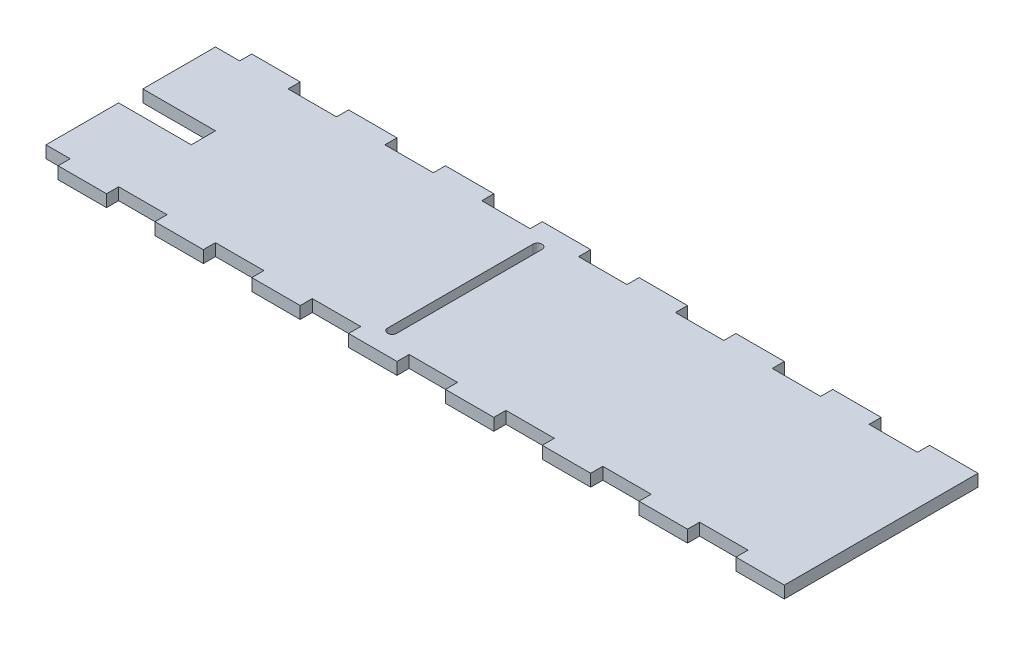
SolidWorks part; units mm, degrees
material "Acrylic (Medium-high impact)"
ref_plane "Front Plane" through (0, 0, 0) normal (0, 0, 1) x (1, 0, 0)
ref_plane "Top Plane" through (0, 0, 0) normal (0, 1, 0) x (1, 0, 0)
ref_plane "Right Plane" through (0, 0, 0) normal (1, 0, 0) x (0, 0, -1)
sketch "Sketch1" plane through (0, 0, 0) normal (0, 1, 0) x (1, 0, 0)
  line L0 (95.25, 0) -> (95.25, -50.8) construction
  line L5 (0, 0) -> (190.5, 0)
  line L6 (0, 0) -> (0, -50.8)
  line L7 (0, -50.8) -> (190.5, -50.8)
  line L8 (190.5, 0) -> (190.5, -50.8)
  line L9 (190.5, -25.4) -> (0, -25.4) construction
  line L14 (12.7, 0) -> (12.7, -3.175)
  line L15 (12.7, -50.8) -> (25.4, -50.8)
  line L16 (12.7, -50.8) -> (12.7, -47.625)
  line L17 (12.7, -47.625) -> (25.4, -47.625)
  line L18 (25.4, -50.8) -> (25.4, -47.625)
  line L19 (12.7, -3.175) -> (25.4, -3.175)
  line L20 (25.4, 0) -> (25.4, -3.175)
  line L21 (38.1, 0) -> (38.1, -3.175)
  line L22 (38.1, -3.175) -> (50.8, -3.175)
  line L23 (50.8, 0) -> (50.8, -3.175)
  line L24 (50.8, -50.8) -> (50.8, -47.625)
  line L25 (38.1, -47.625) -> (50.8, -47.625)
  line L26 (38.1, -50.8) -> (38.1, -47.625)
  line L27 (63.5, 0) -> (63.5, -3.175)
  line L28 (63.5, -3.175) -> (76.2, -3.175)
  line L29 (76.2, 0) -> (76.2, -3.175)
  line L30 (76.2, -50.8) -> (76.2, -47.625)
  line L31 (63.5, -47.625) -> (76.2, -47.625)
  line L32 (63.5, -50.8) -> (63.5, -47.625)
  line L33 (88.9, 0) -> (88.9, -3.175)
  line L34 (88.9, -3.175) -> (101.6, -3.175)
  line L35 (101.6, 0) -> (101.6, -3.175)
  line L36 (101.6, -50.8) -> (101.6, -47.625)
  line L37 (88.9, -47.625) -> (101.6, -47.625)
  line L38 (88.9, -50.8) -> (88.9, -47.625)
  line L39 (114.3, 0) -> (114.3, -3.175)
  line L40 (114.3, -3.175) -> (127, -3.175)
  line L41 (127, 0) -> (127, -3.175)
  line L42 (127, -50.8) -> (127, -47.625)
  line L43 (114.3, -47.625) -> (127, -47.625)
  line L44 (114.3, -50.8) -> (114.3, -47.625)
  line L45 (139.7, 0) -> (139.7, -3.175)
  line L46 (139.7, -3.175) -> (152.4, -3.175)
  line L47 (152.4, 0) -> (152.4, -3.175)
  line L48 (152.4, -50.8) -> (152.4, -47.625)
  line L49 (139.7, -47.625) -> (152.4, -47.625)
  line L50 (139.7, -50.8) -> (139.7, -47.625)
  line L51 (165.1, 0) -> (165.1, -3.175)
  line L52 (165.1, -3.175) -> (177.8, -3.175)
  line L53 (177.8, 0) -> (177.8, -3.175)
  line L54 (177.8, -50.8) -> (177.8, -47.625)
  line L55 (165.1, -47.625) -> (177.8, -47.625)
  line L56 (165.1, -50.8) -> (165.1, -47.625)
  dimension "D1" = 50.8
  dimension "D2" = 190.5
  dimension "D3" = 3.175
  dimension "D4" = 12.7
  dimension "D5" = 12.7
  dimension "D7" = 12.7
  dimension "D6" = 7
extrude "Boss-Extrude1" add sketch "Sketch1" along normal blind 3.175 contours L7 L56 L55 L54 L8 L5 L53 L52 L51 L47 L46 L45 L41 L40 L39 L35 L34 L33 L29 L28 L27 L23 L22 L21 L20 L19 L14 L6 L16 L17 L18 L26 L25 L24 L32 L31 L30 L38 L37 region at (95.25, 0, 25.4)
sketch "Sketch2" plane through (0, 3.175, 0) normal (0, 1, 0) x (1, 0, 0)
  line L2 (0, 0) -> (0, -50.8) construction
  line L3 (0, -28.575) -> (12.7, -28.575)
  line L4 (0, -28.575) -> (0, -22.225)
  line L5 (0, -22.225) -> (12.7, -22.225)
  line L6 (12.7, -28.575) -> (12.7, -22.225)
  point P12 (0, -25.4)
  point P13 (0, -25.4)
  dimension "D3" = 6.35
  dimension "D4" = 12.7
extrude "Cut-Extrude1" cut sketch "Sketch2" against normal through all
sketch "Sketch3" plane through (0, 0, 0) normal (-1, 0, 0) x (0, 0, 1)
  line L1 (3.175, 0) -> (22.225, 0)
  line L2 (3.175, 0) -> (3.175, 3.175)
  line L3 (3.175, 3.175) -> (22.225, 3.175)
  line L4 (22.225, 0) -> (22.225, 3.175)
  line L5 (47.625, 0) -> (28.575, 0)
  line L6 (47.625, 0) -> (47.625, 3.175)
  line L7 (47.625, 3.175) -> (28.575, 3.175)
  line L8 (28.575, 0) -> (28.575, 3.175)
  line L9 (50.8, 3.175) -> (50.8, 0) construction
  line L10 (0, 3.175) -> (0, 0) construction
  line L11 (0, 0) -> (22.225, 0) construction
  dimension "D1" = 3.175
  dimension "D2" = 3.175
extrude "Boss-Extrude2" add sketch "Sketch3" along normal blind 6.35
sketch "Sketch4" plane through (0, 3.175, 0) normal (0, 1, 0) x (1, 0, 0)
  line L0 (166.37, -9.525) -> (166.37, -41.275) construction
  line L1 (167.5689, -9.525) -> (167.5689, -41.275)
  line L2 (165.1711, -9.525) -> (165.1711, -41.275)
  line L3 (190.5, 0) -> (190.5, -50.8) construction
  line L4 (152.4, -50.8) -> (165.1, -50.8) construction
  arc A0 (167.5689, -9.525) -> (165.1711, -9.525) centre (166.37, -9.525) ccw
  arc A1 (165.1711, -41.275) -> (167.5689, -41.275) centre (166.37, -41.275) ccw
  point P2 (166.37, -25.4)
  dimension "D2" = 1.1989
  dimension "D1" = 24.13
  dimension "D3" = 25.4
  dimension "D4" = 31.75
extrude "Cut-Extrude2" [suppressed] cut sketch "Sketch4" against normal up to surface (3.175 mm away)
sketch "Sketch5" plane through (0, 3.175, 0) normal (0, 1, 0) x (1, 0, 0)
  line L0 (81.28, -6.35) -> (81.28, -44.45) construction
  line L1 (82.48, -6.35) -> (82.48, -44.45)
  line L2 (80.08, -6.35) -> (80.08, -44.45)
  line L5 (76.2, -50.8) -> (88.9, -50.8) construction
  arc A0 (82.48, -6.35) -> (80.08, -6.35) centre (81.28, -6.35) ccw
  arc A1 (80.08, -44.45) -> (82.48, -44.45) centre (81.28, -44.45) ccw
  point P2 (81.28, -25.4)
  dimension "D2" = 1.2
  dimension "D1" = 109.22
  dimension "D3" = 38.1
  dimension "D4" = 25.4
extrude "Cut-Extrude4" cut sketch "Sketch5" against normal up to surface (3.175 mm away) contours A1 L1 A0 L2 up to face at (84.0441, 0, 25.4)
sketch "Sketch6" plane through (0, 0, 0) normal (0, -1, 0) x (-1, 0, 0)
  line L0 (-104.14, -44.45) -> (-104.14, -6.35)
  line L5 (-104.14, -44.45) -> (-107.88, -44.45)
  line L6 (-107.88, -44.45) -> (-107.88, -6.35)
  line L7 (-91.44, -44.45) -> (-95.18, -44.45)
  line L8 (-91.44, -44.45) -> (-91.44, -6.35)
  line L9 (-91.44, -6.35) -> (-95.18, -6.35)
  line L10 (-95.18, -44.45) -> (-95.18, -6.35)
  line L11 (-82.48, -44.45) -> (-82.48, -6.35) construction
  line L12 (-104.14, -6.35) -> (-107.88, -6.35)
  line L13 (-116.84, -44.45) -> (-116.84, -6.35)
  line L14 (-116.84, -44.45) -> (-120.58, -44.45)
  line L15 (-120.58, -44.45) -> (-120.58, -6.35)
  line L16 (-116.84, -6.35) -> (-120.58, -6.35)
  line L17 (-129.54, -44.45) -> (-129.54, -6.35)
  line L18 (-129.54, -44.45) -> (-133.28, -44.45)
  line L19 (-133.28, -44.45) -> (-133.28, -6.35)
  line L20 (-129.54, -6.35) -> (-133.28, -6.35)
  line L21 (-142.24, -44.45) -> (-142.24, -6.35)
  line L22 (-142.24, -44.45) -> (-145.98, -44.45)
  line L23 (-145.98, -44.45) -> (-145.98, -6.35)
  line L24 (-142.24, -6.35) -> (-145.98, -6.35)
  arc A0 (-80.08, -6.35) -> (-82.48, -6.35) centre (-81.28, -6.35) ccw construction
  arc A1 (-82.48, -44.45) -> (-80.08, -44.45) centre (-81.28, -44.45) ccw construction
  point P25 (-81.28, -5.15)
  point P31 (-93.31, -44.45)
  dimension "D5" = 0
  dimension "D1" = 5
  dimension "D2" = 0
  dimension "D3" = 10.16
  dimension "D4" = 12.7
  dimension "D6" = 8.96
extrude "Boss-Extrude3" add sketch "Sketch6" along normal blind 2.54 contours L13 L16 L15 L14 | L0 L12 L6 L5 | L8 L9 L10 L7 | L21 L24 L23 L22 | L17 L20 L19 L18
fillet "Fillet1" radius 5.08 10 edges at (93.31, -2.54, 6.35) (106.01, -2.54, 6.35) (118.71, -2.54, 6.35) (131.41, -2.54, 6.35) (144.11, -2.54, 6.35) (144.11, -2.54, 44.45) (131.41, -2.54, 44.45) (118.71, -2.54, 44.45) (106.01, -2.54, 44.45) (93.31, -2.54, 44.45)
sketch "Sketch7" plane through (91.44, 0, 0) normal (-1, 0, 0) x (0, 0, 1)
  line L0 (44.45, 0) -> (6.35, 0) construction
  line L1 (10.7494, 0) -> (40.0506, 0)
  line L2 (10.7494, 0) -> (10.7494, -1.2)
  line L3 (10.7494, -1.2) -> (40.0506, -1.2)
  line L4 (40.0506, 0) -> (40.0506, -1.2)
  dimension "D1" = 1.2
extrude "Cut-Extrude5" cut sketch "Sketch7" against normal up to surface (54.54 mm away) up to face at (145.98, -1.5647, 25.4)
fillet "Fillet3" radius 2.54 10 edges at (131.41, 0, 6.35) (118.71, 0, 6.35) (93.31, 0, 6.35) (106.01, 0, 6.35) (93.31, 0, 44.45) (106.01, 0, 44.45) (118.71, 0, 44.45) (131.41, 0, 44.45) (144.11, 0, 44.45) (144.11, 0, 6.35)
sketch "Sketch9" plane through (-6.35, 0, 0) normal (-1, 0, 0) x (0, 0, 1)
  line L0 (3.175, 0) -> (3.175, 3.175)
  line L1 (3.175, 3.175) -> (22.225, 3.175)
  line L2 (22.225, 3.175) -> (22.225, 0)
  line L3 (22.225, 0) -> (3.175, 0)
  line L4 (28.575, 0) -> (28.575, 3.175)
  line L5 (28.575, 3.175) -> (47.625, 3.175)
  line L6 (47.625, 3.175) -> (47.625, 0)
  line L7 (47.625, 0) -> (28.575, 0)
